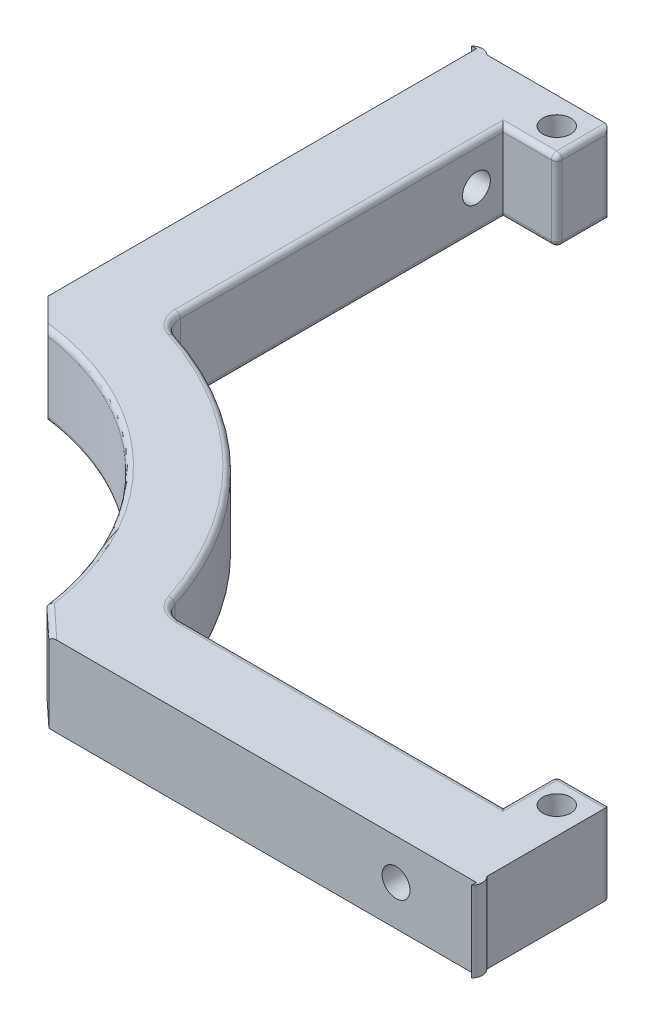
SolidWorks part; units mm, degrees
ref_plane "Front Plane" through (0, 0, 0) normal (0, 0, 1) x (1, 0, 0)
ref_plane "Top Plane" through (0, 0, 0) normal (0, 1, 0) x (1, 0, 0)
ref_plane "Right Plane" through (0, 0, 0) normal (1, 0, 0) x (0, 0, -1)
sketch "Sketch1" plane through (0, 0, 0) normal (0, 1, 0) x (1, 0, 0)
  line L2 (0, 0) -> (0, -107.95)
  line L3 (-2.3808, -173.5658) -> (164.9741, -6.2109) construction
  line L8 (31.75, 0) -> (31.75, -12.7)
  line L9 (31.75, -12.7) -> (19.05, -12.7)
  line L10 (19.05, -12.7) -> (19.05, -93.012)
  line L12 (158.485, -152.135) -> (78.173, -152.135)
  line L13 (158.485, -139.435) -> (158.485, -152.135)
  line L14 (171.185, -139.435) -> (158.485, -139.435)
  line L21 (171.185, -171.185) -> (63.235, -171.185)
  line L26 (-1.143, 2.54) -> (-1.143, 0)
  line L27 (-1.143, 0) -> (0, 0)
  line L28 (2.54, 0) -> (31.75, 0)
  line L31 (173.725, -172.328) -> (171.185, -172.328)
  line L32 (171.185, -172.328) -> (171.185, -171.185)
  line L33 (171.185, -168.645) -> (171.185, -139.435)
  line L34 (2.54, 0) -> (-1.143, 2.54)
  line L35 (173.725, -172.328) -> (171.185, -168.645)
  arc A0 (0, -107.95) -> (63.235, -171.185) centre (-2.3808, -173.5658) cw
  arc A1 (19.05, -93.012) -> (78.173, -152.135) centre (-3.1739, -174.3589) cw
  circle A2 centre (25.4, -6.35) radius 3.302
  circle A3 centre (164.835, -145.785) radius 3.302
  dimension "D4" = 65.659
  dimension "D5" = 87.4831
  dimension "D7" = 84.328
  dimension "D15" = 6.604
  dimension "D3" = 98.3742
  dimension "D9" = 2.54
  dimension "D2" = 45
  dimension "D6" = 19.05
  dimension "D8" = 6.35
  dimension "D10" = 2.54
  dimension "D11" = 1.143
  dimension "D12" = 2.54
  dimension "D13" = 12.7
  dimension "D14" = 12.7
  dimension "D16" = 1.143
  dimension "D17" = 6.35
  dimension "D18" = 107.95
  dimension "D19" = 2.54
extrude "Boss-Extrude1" add sketch "Sketch1" along normal blind 19.05
chamfer "Chamfer1" distance 6.35 angle 45 2 edges at (63.235, 9.525, 171.185) (0, 9.525, 107.95)
fillet "Fillet1" radius 5.08 2 edges at (78.173, 9.525, 152.135) (19.05, 9.525, 93.012)
fillet "Fillet2" radius 1.27 25 edges at (120.224, 0, 152.135) (78.9692, 0, 151.1591) (19.05, 0, 50.961) (20.0259, 0, 92.2158) (120.224, 19.05, 152.135) (78.9692, 19.05, 151.1591) (19.05, 19.05, 50.961) (20.0259, 19.05, 92.2158) (158.485, 0, 145.785) (164.835, 0, 139.435) (158.485, 9.525, 139.435) (31.75, 0, 6.35) (31.75, 9.525, 12.7) (31.75, 19.05, 6.35) (25.4, 19.05, 12.7) (25.4, 0, 12.7) (44.1548, 0, 127.2459) (164.835, 19.05, 139.435) (158.485, 19.05, 145.785) (66.2395, 19.05, 167.8474) (44.1548, 19.05, 127.2459) (56.455, 0, 114.73) (56.455, 19.05, 114.73) (31.75, 9.525, 0) (171.185, 9.525, 139.435)
sketch "Sketch4" plane through (19.05, 0, 0) normal (1, 0, 0) x (0, 0, -1)
  line L0 (-12.7, 17.78) -> (-12.7, 1.27) construction
  circle A0 centre (-19.05, 9.525) radius 3.302
  point P4 (-12.7, 9.525)
  dimension "D2" = 6.604
  dimension "D1" = 6.35
extrude "Cut-Extrude3" cut sketch "Sketch4" against normal up to next
sketch "Sketch5" plane through (0, 0, 152.135) normal (0, 0, -1) x (-1, 0, 0)
  line L0 (-158.485, 17.78) -> (-158.485, 1.27) construction
  circle A0 centre (-152.135, 9.525) radius 3.302
  point P4 (-158.485, 9.525)
  dimension "D1" = 6.604
  dimension "D2" = 6.35
extrude "Cut-Extrude4" cut sketch "Sketch5" against normal up to next
fillet "Fillet27" radius 2.54 2 edges at (-1.143, 9.525, -2.54) (173.725, 9.525, 172.328)
